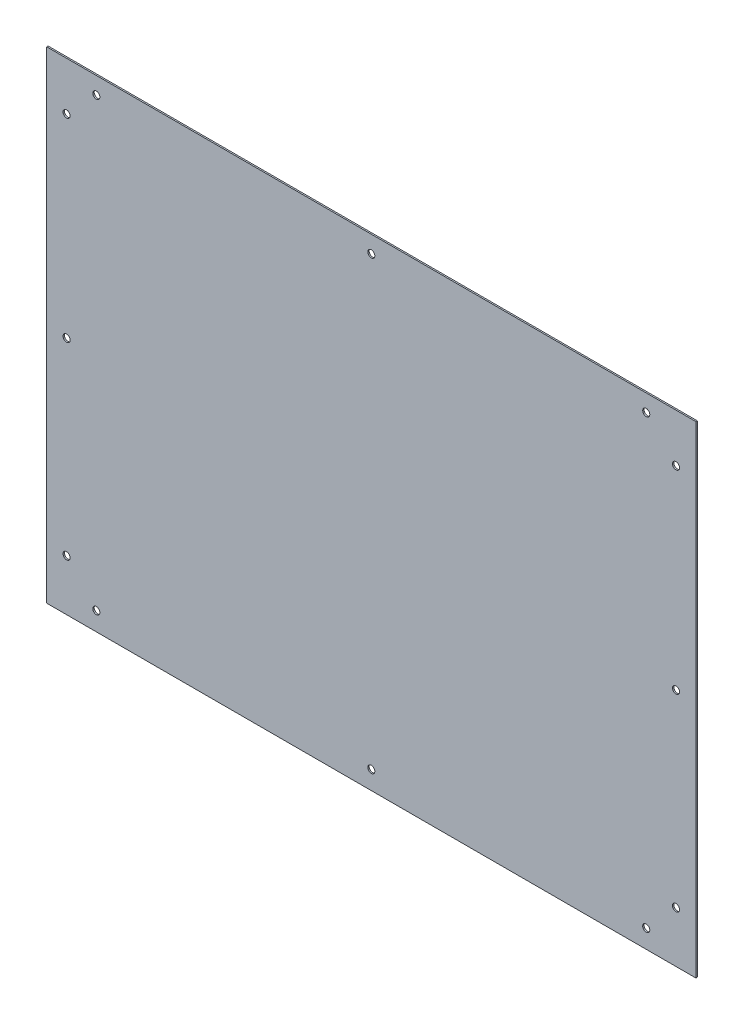
SolidWorks part; units mm, degrees
material "1345 Alloy"
ref_plane "Front Plane" through (0, 0, 0) normal (0, 0, 1) x (1, 0, 0)
ref_plane "Top Plane" through (0, 0, 0) normal (0, 1, 0) x (1, 0, 0)
ref_plane "Right Plane" through (0, 0, 0) normal (1, 0, 0) x (0, 0, -1)
sketch "Sketch1" plane through (0, 0, 0) normal (0, 0, 1) x (1, 0, 0)
  line L1 (-229, 169) -> (229, 169)
  line L2 (-229, 169) -> (-229, -169)
  line L3 (-229, -169) -> (229, -169)
  line L4 (229, 169) -> (229, -169)
  line L5 (-229, 169) -> (229, -169) construction
  line L6 (-229, -169) -> (229, 169) construction
  point P0 (0, 0)
  dimension "D1" = 458
  dimension "D2" = 338
extrude "Boss-Extrude1" add sketch "Sketch1" along normal blind 1
sketch "Sketch2" plane through (0, 0, 1) normal (0, 0, 1) x (1, 0, 0)
  line L4 (-194.0026, -156) -> (193.9974, -156) construction
  line L5 (-215, 137) -> (-215, -133) construction
  line L6 (215, 137) -> (215, -133) construction
  line L8 (194, 159) -> (194, 169) construction
  line L11 (-229, -169) -> (229, -169) construction
  line L12 (229, 0) -> (215, 0) construction
  line L14 (229, 169) -> (-229, 169) construction
  circle A0 centre (-194, 159) radius 2.5
  circle A1 centre (-194.0026, -156) radius 2.5
  circle A2 centre (193.9974, -156) radius 2.5
  circle A3 centre (194, 159) radius 2.5
  circle A4 centre (-215, 0) radius 2.5
  circle A5 centre (-215, -133) radius 2.5
  circle A6 centre (-215, 137) radius 2.5
  circle A7 centre (215, 0) radius 2.5
  circle A8 centre (215, -133) radius 2.5
  circle A9 centre (215, 137) radius 2.5
  circle A10 centre (0, 159) radius 2.5
  circle A11 centre (-0.0026, -156) radius 2.5
  dimension "D3" = 5
  dimension "D6" = 5
  dimension "D7" = 5
  dimension "D8" = 5
  dimension "D13" = 5
  dimension "D14" = 5
  dimension "D15" = 5
  dimension "D19" = 5
  dimension "D20" = 5
  dimension "D4" = 215
  dimension "D5" = 215
  dimension "D9" = 13
  dimension "D11" = 36
  dimension "D18" = 13
  dimension "D21" = 194
  dimension "D24" = 194
  dimension "D26" = 32
  dimension "D27" = 137
extrude "Cut-Extrude1" cut sketch "Sketch2" against normal through all
sketch "Sketch3" plane through (0, 0, 1) normal (0, 0, 1) x (1, 0, 0)
  line L1 (-229, 169) -> (229, 169)
  line L2 (-229, 169) -> (-229, 171)
  line L3 (-229, 171) -> (229, 171)
  line L4 (229, 169) -> (229, 171)
  dimension "D1" = 458
  dimension "D2" = 2
extrude "Boss-Extrude2" add sketch "Sketch3" against normal through all
